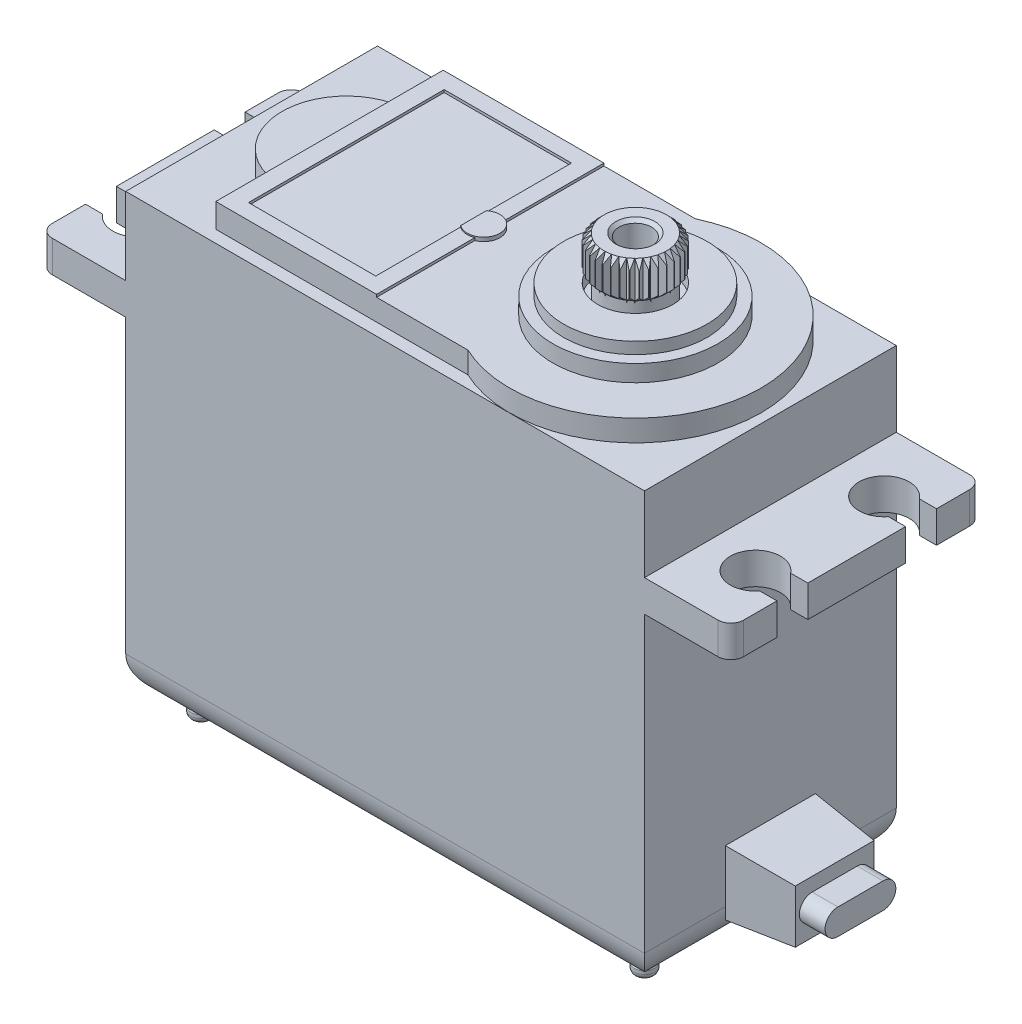
SolidWorks part; units mm, degrees
ref_plane "Front Plane" through (0, 0, 0) normal (0, 0, 1) x (1, 0, 0)
ref_plane "Top Plane" through (0, 0, 0) normal (0, 1, 0) x (1, 0, 0)
ref_plane "Right Plane" through (0, 0, 0) normal (1, 0, 0) x (0, 0, -1)
sketch "Sketch1" plane through (0, 0, 0) normal (0, 1, 0) x (1, 0, 0)
  line L1 (-18.6567, 11.3793) -> (21.6633, 11.3793)
  line L2 (-18.6567, 11.3793) -> (-18.6567, -8.1907)
  line L3 (-18.6567, -8.1907) -> (21.6633, -8.1907)
  line L4 (21.6633, 11.3793) -> (21.6633, -8.1907)
extrude "Boss-Extrude1" add sketch "Sketch1" along normal blind 35.37
sketch "Sketch2" plane through (21.6633, 0, 0) normal (1, 0, 0) x (0, 0, -1)
  line L0 (-8.1907, 0) -> (-8.1907, 3)
  line L1 (-8.1907, 35.37) -> (-8.1907, 0) construction
  line L2 (-8.1907, 3) -> (-5.1907, 0)
  line L3 (-8.1907, 0) -> (11.3793, 0) construction
  line L4 (-5.1907, 0) -> (-8.1907, 0)
  line L5 (1.5943, 0) -> (1.5943, 35.37) construction
  line L6 (-8.1907, 35.37) -> (11.3793, 35.37) construction
  line L7 (8.3793, 0) -> (11.3793, 0)
  line L8 (11.3793, 3) -> (8.3793, 0)
  line L9 (11.3793, 0) -> (11.3793, 3)
extrude "Cut-Extrude1" cut sketch "Sketch2" against normal up to next
sketch "Sketch3" plane through (0, 0, 8.1907) normal (0, 0, 1) x (1, 0, 0)
  line L0 (21.6633, 0) -> (18.6633, 0)
  line L1 (-18.6567, 0) -> (21.6633, 0) construction
  line L2 (18.6633, 0) -> (21.6633, 3)
  line L3 (21.6633, 35.37) -> (21.6633, 3) construction
  line L4 (21.6633, 3) -> (21.6633, 0)
  line L5 (1.5033, 35.37) -> (1.5033, 0) construction
  line L6 (-18.6567, 35.37) -> (21.6633, 35.37) construction
  line L7 (-18.6567, 3) -> (-18.6567, 0)
  line L8 (-15.6567, 0) -> (-18.6567, 3)
  line L9 (-18.6567, 0) -> (-15.6567, 0)
extrude "Cut-Extrude2" cut sketch "Sketch3" against normal up to next
fillet "Fillet2" radius 3 4 edges at (21.6633, 3, -1.5943) (1.5033, 3, 8.1907) (-18.6567, 3, -1.5943) (1.5033, 3, -11.3793)
sketch "Sketch5" plane through (21.6633, 0, 0) normal (1, 0, 0) x (0, 0, -1)
  line L0 (1.5943, 35.37) -> (1.5943, 29.53) construction
  line L1 (-8.1907, 35.37) -> (11.3793, 35.37) construction
  line L2 (-8.1907, 29.53) -> (1.5943, 29.53)
  line L3 (-8.1907, 35.37) -> (-8.1907, 4.2426) construction
  line L4 (1.5943, 29.53) -> (11.3793, 29.53)
  line L5 (11.3793, 35.37) -> (11.3793, 4.2426) construction
  line L6 (11.3793, 29.53) -> (11.3793, 27.07)
  line L7 (11.3793, 27.07) -> (-8.1907, 27.07)
  line L8 (-8.1907, 27.07) -> (-8.1907, 29.53)
extrude "Boss-Extrude2" add sketch "Sketch5" along normal blind 6.71
sketch "Sketch7" plane through (-18.6567, 0, 0) normal (-1, 0, 0) x (0, 0, 1)
  line L0 (-1.5943, 35.37) -> (-1.5943, 29.3613) construction
  line L1 (-11.3793, 29.3613) -> (-1.5943, 29.3613)
  line L2 (-1.5943, 29.3613) -> (8.1907, 29.3613)
  line L3 (8.1907, 29.3613) -> (8.1907, 26.9013)
  line L4 (8.1907, 26.9013) -> (-11.3793, 26.9013)
  line L5 (-11.3793, 26.9013) -> (-11.3793, 29.3613)
  line L6 (-11.3793, 35.37) -> (8.1907, 35.37) construction
  line L7 (8.1907, 35.37) -> (8.1907, 4.2426) construction
  line L8 (-11.3793, 35.37) -> (-11.3793, 4.2426) construction
extrude "Boss-Extrude3" add sketch "Sketch7" along normal blind 6.71
sketch "Sketch8" plane through (0, 29.53, 0) normal (0, 1, 0) x (1, 0, 0)
  line L0 (28.3733, 1.5943) -> (-25.3667, 1.5943) construction
  line L2 (-25.3667, -8.1907) -> (-25.3667, 11.3793) construction
  line L4 (28.3733, -2.2057) -> (27.0403, -2.2057)
  line L5 (28.3733, 11.3793) -> (28.3733, -8.1907) construction
  line L6 (28.3733, 5.9709) -> (28.3733, 7.7943)
  line L7 (28.3733, 7.7943) -> (27.0403, 7.7943)
  line L8 (28.3733, 5.9709) -> (28.3733, 5.3943)
  line L9 (28.3733, 5.3943) -> (27.0403, 5.3943)
  line L10 (28.3733, -2.7824) -> (28.3733, -2.2057)
  line L11 (28.3733, -4.6057) -> (27.0403, -4.6057)
  line L12 (28.3733, -2.7824) -> (28.3733, -4.6057)
  line L13 (1.5033, 11.3793) -> (1.5033, -8.1907) construction
  line L14 (21.6633, 11.3793) -> (-18.6567, 11.3793) construction
  line L15 (-18.6567, -8.1907) -> (21.6633, -8.1907) construction
  line L24 (-25.3667, 5.3943) -> (-24.0337, 5.3943)
  line L25 (-25.3667, -2.7824) -> (-25.3667, -4.6057)
  line L26 (-25.3667, -4.6057) -> (-24.0337, -4.6057)
  line L27 (-25.3667, -2.7824) -> (-25.3667, -2.2057)
  line L28 (-25.3667, -2.2057) -> (-24.0337, -2.2057)
  line L29 (-25.3667, 5.9709) -> (-25.3667, 5.3943)
  line L30 (-25.3667, 7.7943) -> (-24.0337, 7.7943)
  line L31 (-25.3667, 5.9709) -> (-25.3667, 7.7943)
  arc A0 (27.0403, -2.2057) -> (27.0403, -4.6057) centre (25.5033, -3.4057) ccw
  arc A1 (27.0403, 5.3943) -> (27.0403, 7.7943) centre (25.5033, 6.5943) cw
  arc A4 (-24.0337, 5.3943) -> (-24.0337, 7.7943) centre (-22.4967, 6.5943) ccw
  arc A5 (-24.0337, -2.2057) -> (-24.0337, -4.6057) centre (-22.4967, -3.4057) cw
  dimension "D1" = 10
  dimension "D2" = 48
extrude "Cut-Extrude3" cut sketch "Sketch8" against normal up to next
sketch "Sketch9" plane through (0, 35.37, 0) normal (0, 1, 0) x (1, 0, 0)
  line L0 (6.9933, -8.1907) -> (6.9933, -7.2426) construction
  line L1 (-18.6567, 6.4311) -> (-12.6067, 6.4311) construction
  line L2 (6.9933, 11.3793) -> (6.9933, 10.4311) construction
  line L3 (-18.6567, -3.2426) -> (-12.6067, -3.2426) construction
  line L4 (-18.6567, -8.1907) -> (-18.6567, 11.3793) construction
  line L5 (-18.6567, 1.5943) -> (21.6633, 1.5943) construction
  line L6 (-12.6067, 10.4311) -> (6.9933, 10.4311)
  line L7 (-18.6567, 11.3793) -> (-18.6567, -8.1907) construction
  line L8 (-12.6067, -7.2426) -> (-12.6067, -3.2426)
  line L9 (21.6633, -8.1907) -> (21.6633, 11.3793) construction
  line L10 (-12.6067, 10.4311) -> (-12.6067, 6.4311)
  line L11 (-12.6067, -7.2426) -> (6.9933, -7.2426)
  line L12 (21.6633, 1.5943) -> (20.9438, 1.5943) construction
  line L13 (21.6633, 11.3793) -> (-18.6567, 11.3793) construction
  arc A0 (6.9933, 10.4311) -> (6.9933, -7.2426) centre (11.1697, 1.5943) cw
  arc A1 (-12.6067, 6.4311) -> (-12.6067, -3.2426) centre (-11.2767, 1.5943) ccw
extrude "Boss-Extrude4" add sketch "Sketch9" along normal blind 1.67
sketch "Sketch10" plane through (0, 37.04, 0) normal (0, 1, 0) x (1, 0, 0)
  circle A1 centre (11.1697, 1.5943) radius 6.415
extrude "Boss-Extrude5" add sketch "Sketch10" along normal blind 1.3
sketch "Sketch11" plane through (0, 38.34, 0) normal (0, 1, 0) x (-1, 0, 0)
  circle A2 centre (-11.1697, -1.5943) radius 5.575
extrude "Boss-Extrude6" add sketch "Sketch11" along normal blind 0.9
sketch "Sketch12" plane through (0, 39.24, 0) normal (0, 1, 0) x (1, 0, 0)
  circle A1 centre (11.1697, 1.5943) radius 2.925
extrude "Cut-Extrude4" cut sketch "Sketch12" against normal blind 1
sketch "Sketch13" plane through (0, 38.24, 0) normal (0, 1, 0) x (-1, 0, 0)
  circle A0 centre (-11.1697, -1.5943) radius 2.425
extrude "Boss-Extrude7" add sketch "Sketch13" along normal blind 1.5
sketch "Sketch14" plane through (0, 39.74, 0) normal (0, 1, 0) x (1, 0, 0)
  circle A0 centre (11.1697, 1.5943) radius 2.925
extrude "Boss-Extrude8" add sketch "Sketch14" along normal blind 2.86
sketch "Sketch15" plane through (0, 42.6, 0) normal (0, 1, 0) x (1, 0, 0)
  circle A0 centre (11.1697, 1.5943) radius 1.27
extrude "Cut-Extrude5" cut sketch "Sketch15" against normal blind 7
sketch "Sketch16" plane through (0, 37.04, 0) normal (0, 1, 0) x (1, 0, 0)
  line L0 (-12.6067, -7.2426) -> (6.9933, -7.2426) construction
  line L1 (-12.6067, 10.4311) -> (-0.1067, 10.4311)
  line L2 (-12.6067, 10.4311) -> (-12.6067, -7.2426)
  line L3 (-12.6067, -7.2426) -> (-0.1067, -7.2426)
  line L4 (-0.1067, 10.4311) -> (-0.1067, -7.2426)
  line L5 (-6.3168, 9.1673) -> (-6.3567, 10.4311) construction
  line L6 (-11.2628, 9.1673) -> (-1.3708, 9.1673)
  line L7 (-11.2628, 9.1673) -> (-11.2628, -6.0433)
  line L8 (-11.2628, -6.0433) -> (-1.3708, -6.0433)
  line L9 (-1.3708, 9.1673) -> (-1.3708, 1.562)
  line L10 (-11.2628, 1.562) -> (-12.6067, 1.5943) construction
  line L11 (-1.3708, 1.562) -> (-0.1067, 1.5943) construction
  line L12 (-6.3168, -6.0433) -> (-6.3567, -7.2426) construction
  line L13 (-1.3708, 1.562) -> (-1.3708, -6.0433)
extrude "Boss-Extrude9" add sketch "Sketch16" along normal blind 0.2
sketch "Sketch17" plane through (0, 37.24, 0) normal (0, 1, 0) x (-1, 0, 0)
  line L0 (1.3708, -1.562) -> (1.3708, -2.562)
  line L1 (1.3708, 6.0433) -> (1.3708, -9.1673) construction
  line L2 (1.3708, -1.562) -> (1.3708, -0.562)
  arc A0 (1.3708, -2.562) -> (1.3708, -0.562) centre (0.592, -1.562) cw
extrude "Boss-Extrude10" add sketch "Sketch17" along normal blind 0.1 and the other way blind 0.5
sketch "Sketch19" plane through (0, 42.6, 0) normal (0, 1, 0) x (1, 0, 0)
  line L0 (10.8404, 4.5007) -> (11.3402, 4.5143) construction
  line L1 (11.3402, 4.5143) -> (11.0903, 4.0075)
  line L2 (11.0903, 4.0075) -> (10.8404, 4.5007)
  line L3 (11.0903, 4.5075) -> (11.0903, 4.0075) construction
  line L4 (10.8404, 4.5007) -> (10.7613, 4.6463)
  line L5 (11.3402, 4.5143) -> (11.4053, 4.6463)
  line L6 (10.7613, 4.6463) -> (11.4053, 4.6463)
  circle A3 centre (11.1697, 1.5943) radius 2.925 construction
  circle A4 centre (11.1697, 1.5943) radius 2.925 construction
extrude "Cut-Extrude11" cut sketch "Sketch19" against normal blind 3
sketch "Sketch21" plane through (0, 0, 0) normal (0, -1, 0) x (1, 0, 0)
  line L0 (1.5033, 5.1907) -> (1.5033, -8.3793) construction
  line L1 (20.7846, 7.3121) -> (17.7846, 7.3121)
  line L2 (20.7846, 7.3121) -> (20.7846, 4.3121)
  line L3 (20.7846, 4.3121) -> (17.7846, 4.3121)
  line L4 (17.7846, 7.3121) -> (17.7846, 4.3121)
  line L5 (-15.6567, 5.1907) -> (18.6633, 5.1907) construction
  line L6 (-15.6567, -8.3793) -> (18.6633, -8.3793) construction
  line L7 (-15.6567, -1.5943) -> (18.6633, -1.5943) construction
  line L8 (-15.6567, -8.3793) -> (-15.6567, 5.1907) construction
  line L9 (18.6633, -8.3793) -> (18.6633, 5.1907) construction
  line L10 (17.7846, -10.5006) -> (17.7846, -7.5006)
  line L11 (20.7846, -7.5006) -> (17.7846, -7.5006)
  line L12 (20.7846, -10.5006) -> (20.7846, -7.5006)
  line L13 (20.7846, -10.5006) -> (17.7846, -10.5006)
  line L14 (-17.778, -7.5006) -> (-14.778, -7.5006)
  line L15 (-14.778, -10.5006) -> (-14.778, -7.5006)
  line L16 (-14.778, 7.3121) -> (-14.778, 4.3121)
  line L17 (-17.778, 4.3121) -> (-14.778, 4.3121)
  line L18 (-17.778, -10.5006) -> (-14.778, -10.5006)
  line L19 (-17.778, -10.5006) -> (-17.778, -7.5006)
  line L20 (-17.778, 7.3121) -> (-17.778, 4.3121)
  line L21 (-17.778, 7.3121) -> (-14.778, 7.3121)
extrude "Cut-Extrude12" cut sketch "Sketch21" against normal blind 1
fillet "Fillet4" radius 1 4 edges at (-14.778, 0.5, -7.5006) (-14.778, 0.5, 4.3121) (17.7846, 0.5, -7.5006) (17.7846, 0.5, 4.3121)
fillet "Fillet5" radius 1 4 edges at (-25.3667, 28.1313, 8.1907) (-25.3667, 28.1313, -11.3793) (28.3733, 28.3, -11.3793) (28.3733, 28.3, 8.1907)
chamfer "Chamfer2" distance 0.5 angle 45 2 edges at (11.2493, 42.6, 1.3297) (11.2493, 39.74, 1.3297)
chamfer "Chamfer3" distance 0.25 angle 45 1 edges at (11.1697, 42.6, -0.3243)
pattern_circular "CirPattern12" count 34 over 360 about axis through (11.1697, 42.6, -1.5943) along (0, -1, 0) of "Cut-Extrude11"
sketch "Sketch23" plane through (0, 1, 0) normal (0, -1, 0) x (1, 0, 0)
  line L0 (1.5033, 5.1907) -> (1.5033, -8.3793) construction
  line L1 (-14.7854, 5.1907) -> (17.792, 5.1907) construction
  line L2 (-14.7854, -8.3793) -> (17.792, -8.3793) construction
  line L3 (18.6633, -1.5943) -> (-15.6567, -1.5943) construction
  line L4 (18.6633, -7.508) -> (18.6633, 4.3195) construction
  line L5 (-15.6567, -7.508) -> (-15.6567, 4.3195) construction
  circle A0 centre (18.7344, -8.4503) radius 0.4237
  circle A1 centre (18.7344, 5.2618) radius 0.4237
  circle A2 centre (-15.7278, 5.2618) radius 0.4237
  circle A3 centre (-15.7278, -8.4503) radius 0.4237
extrude "Boss-Extrude12" add sketch "Sketch23" along normal blind 0.1
sketch "Sketch24" plane through (0, 0.9, 0) normal (0, -1, 0) x (1, 0, 0)
  line L0 (1.5033, 5.1907) -> (1.5033, -8.3793) construction
  line L1 (-14.7854, 5.1907) -> (17.792, 5.1907) construction
  line L2 (-14.7854, -8.3793) -> (17.792, -8.3793) construction
  line L3 (18.6633, -1.5943) -> (-15.6567, -1.5943) construction
  line L4 (18.6633, -7.508) -> (18.6633, 4.3195) construction
  line L5 (-15.6567, -7.508) -> (-15.6567, 4.3195) construction
  circle A0 centre (18.7344, -8.4503) radius 0.8
  circle A1 centre (18.7344, 5.2618) radius 0.8
  circle A2 centre (-15.7278, 5.2618) radius 0.8
  circle A3 centre (-15.7278, -8.4503) radius 0.8
extrude "Boss-Extrude13" add sketch "Sketch24" along normal blind 0.9
fillet "Fillet8" radius 0.45 4 edges at (18.7344, 0, -9.2503) (-15.7278, 0, -7.6503) (-15.7278, 0, 4.4618) (18.7344, 0, 6.0618)
fillet "Fillet9" radius 0.2 4 edges at (-15.7278, 0.9, -7.6503) (-15.7278, 0.9, 4.4618) (18.7344, 0.9, 6.0618) (18.7344, 0.9, -9.2503)
sketch "Sketch25" plane through (0, 0, 0) normal (0, -1, 0) x (1, 0, 0)
  line L0 (18.0844, 5.3868) -> (18.0844, 5.1368)
  line L1 (18.6094, 4.6118) -> (18.8594, 4.6118)
  line L2 (18.0844, 5.3868) -> (18.6094, 5.3868)
  line L3 (18.6094, 5.3868) -> (18.6094, 5.9118)
  line L4 (19.3844, 5.1368) -> (19.3844, 5.3868)
  line L5 (18.8594, 5.9118) -> (18.6094, 5.9118)
  line L6 (1.5033, 5.1907) -> (1.5033, -8.3793) construction
  line L7 (-14.7854, 5.1907) -> (17.792, 5.1907) construction
  line L8 (-14.7854, -8.3793) -> (17.792, -8.3793) construction
  line L9 (18.6633, -1.5943) -> (-15.6567, -1.5943) construction
  line L10 (18.6633, -7.508) -> (18.6633, 4.3195) construction
  line L11 (-15.6567, -7.508) -> (-15.6567, 4.3195) construction
  line L12 (18.6094, -8.3253) -> (18.0844, -8.3253)
  line L13 (18.6094, -7.8003) -> (18.6094, -8.3253)
  line L14 (18.8594, -8.3253) -> (18.8594, -7.8003)
  line L15 (19.3844, -8.3253) -> (18.8594, -8.3253)
  line L16 (18.8594, -8.5753) -> (19.3844, -8.5753)
  line L17 (18.8594, 5.9118) -> (18.8594, 5.3868)
  line L18 (18.8594, 5.3868) -> (19.3844, 5.3868)
  line L19 (18.8594, -9.1003) -> (18.8594, -8.5753)
  line L20 (19.3844, 5.1368) -> (18.8594, 5.1368)
  line L21 (18.8594, 5.1368) -> (18.8594, 4.6118)
  line L22 (18.8594, -9.1003) -> (18.6094, -9.1003)
  line L23 (18.6094, 4.6118) -> (18.6094, 5.1368)
  line L24 (18.6094, 5.1368) -> (18.0844, 5.1368)
  line L25 (19.3844, -8.3253) -> (19.3844, -8.5753)
  line L26 (18.6094, -8.5753) -> (18.6094, -9.1003)
  line L27 (18.0844, -8.5753) -> (18.6094, -8.5753)
  line L28 (18.6094, -7.8003) -> (18.8594, -7.8003)
  line L29 (18.0844, -8.5753) -> (18.0844, -8.3253)
  line L30 (-15.0778, -8.5753) -> (-15.0778, -8.3253)
  line L31 (-15.6028, -7.8003) -> (-15.8528, -7.8003)
  line L32 (-15.0778, -8.5753) -> (-15.6028, -8.5753)
  line L33 (-15.6028, -8.5753) -> (-15.6028, -9.1003)
  line L34 (-16.3778, -8.3253) -> (-16.3778, -8.5753)
  line L35 (-15.6028, 5.1368) -> (-15.0778, 5.1368)
  line L36 (-15.6028, 4.6118) -> (-15.6028, 5.1368)
  line L37 (-15.8528, -9.1003) -> (-15.6028, -9.1003)
  line L38 (-15.8528, 5.1368) -> (-15.8528, 4.6118)
  line L39 (-16.3778, 5.1368) -> (-15.8528, 5.1368)
  line L40 (-15.8528, -9.1003) -> (-15.8528, -8.5753)
  line L41 (-15.8528, 5.3868) -> (-16.3778, 5.3868)
  line L42 (-15.8528, 5.9118) -> (-15.8528, 5.3868)
  line L43 (-15.8528, -8.5753) -> (-16.3778, -8.5753)
  line L44 (-16.3778, -8.3253) -> (-15.8528, -8.3253)
  line L45 (-15.8528, -8.3253) -> (-15.8528, -7.8003)
  line L46 (-15.6028, -7.8003) -> (-15.6028, -8.3253)
  line L47 (-15.6028, -8.3253) -> (-15.0778, -8.3253)
  line L48 (-15.8528, 5.9118) -> (-15.6028, 5.9118)
  line L49 (-16.3778, 5.1368) -> (-16.3778, 5.3868)
  line L50 (-15.6028, 5.3868) -> (-15.6028, 5.9118)
  line L51 (-15.0778, 5.3868) -> (-15.6028, 5.3868)
  line L52 (-15.6028, 4.6118) -> (-15.8528, 4.6118)
  line L53 (-15.0778, 5.3868) -> (-15.0778, 5.1368)
extrude "Cut-Extrude14" cut sketch "Sketch25" against normal blind 0.6
sketch "Esboço2" plane through (21.6633, 0, 0) normal (1, 0, 0) x (0, 0, -1)
  line L1 (-1.9057, 8.35) -> (5.0943, 8.35)
  line L2 (-1.9057, 8.35) -> (-1.9057, 3.35)
  line L3 (-1.9057, 3.35) -> (5.0943, 3.35)
  line L4 (5.0943, 8.35) -> (5.0943, 3.35)
  line L5 (1.5943, 0) -> (1.5943, 11.1519) construction
  line L6 (7.508, 0) -> (-4.3195, 0) construction
  point P8 (1.5943, 3.35)
  dimension "D1" = 7
  dimension "D2" = 5
  dimension "D3" = 3.35
extrude "Ressalto-extrusão1" add sketch "Esboço2" along normal blind 5 draft 5
sketch "Esboço3" plane through (26.6633, 0, 0) normal (1, 0, 0) x (0, 0, -1)
  line L0 (-0.1557, 5.85) -> (3.3443, 5.85) construction
  line L1 (-0.1557, 6.85) -> (3.3443, 6.85)
  line L2 (-0.1557, 4.85) -> (3.3443, 4.85)
  line L3 (-1.4683, 7.9126) -> (-1.4683, 3.7874) construction
  line L4 (4.6568, 7.9126) -> (-1.4683, 7.9126) construction
  arc A0 (-0.1557, 6.85) -> (-0.1557, 4.85) centre (-0.1557, 5.85) ccw
  arc A1 (3.3443, 4.85) -> (3.3443, 6.85) centre (3.3443, 5.85) ccw
  point P2 (1.5943, 5.85)
  point P9 (-1.4683, 5.85)
  point P12 (1.5943, 7.9126)
  dimension "D2" = 1
  dimension "D1" = 3.5
extrude "Ressalto-extrusão2" add sketch "Esboço3" along normal blind 2 contours L1 A1 L2 A0
